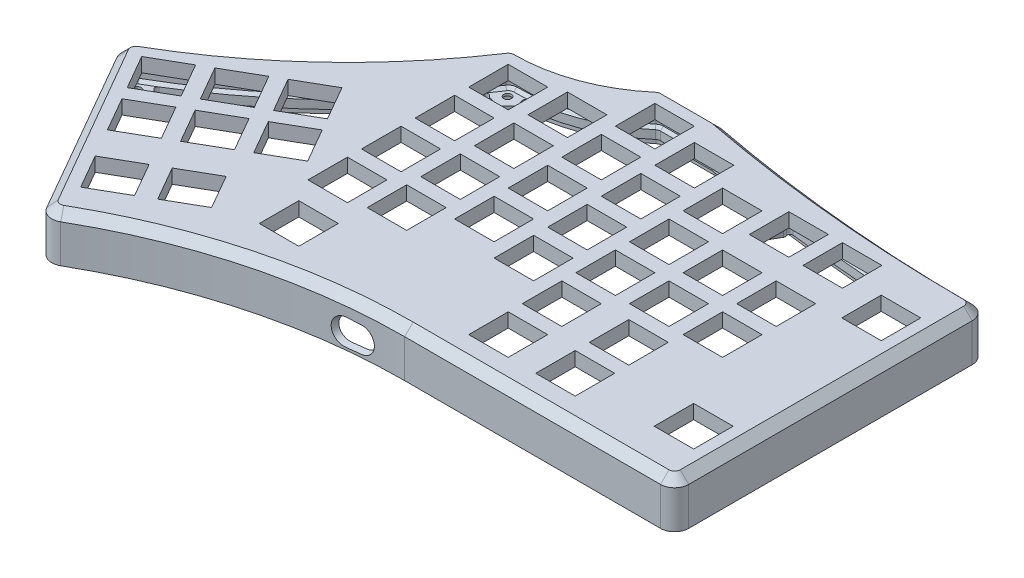
SolidWorks part; units mm, degrees
ref_plane "Front Plane" through (0, 0, 0) normal (0, 0, 1) x (1, 0, 0)
ref_plane "Top Plane" through (0, 0, 0) normal (0, 1, 0) x (1, 0, 0)
ref_plane "Right Plane" through (0, 0, 0) normal (1, 0, 0) x (0, 0, -1)
sketch "Main" plane through (0, 0, 0) normal (0, 1, 0) x (1, 0, 0)
  line L0 (6.4754, 3.5) -> (12.8, 6.5) construction
  line L1 (0, 0) -> (18, 0) construction
  line L2 (0, 0) -> (0, 18) construction
  line L3 (0, 18) -> (18, 18) construction
  line L4 (18, 0) -> (18, 18) construction
  line L5 (2, 16) -> (16, 16)
  line L6 (2, 16) -> (2, 2)
  line L7 (2, 2) -> (16, 2)
  line L8 (16, 16) -> (16, 2)
  line L18 (9, 9) -> (6.4754, 3.5) construction
  line L20 (9, 9) -> (12.8, 6.5) construction
  line L22 (25.4754, 5.5) -> (31.8, 8.5) construction
  line L23 (19, 2) -> (37, 2) construction
  line L24 (19, 2) -> (19, 20) construction
  line L25 (19, 20) -> (37, 20) construction
  line L26 (37, 2) -> (37, 20) construction
  line L27 (21, 18) -> (35, 18)
  line L28 (21, 18) -> (21, 4)
  line L29 (21, 4) -> (35, 4)
  line L30 (35, 18) -> (35, 4)
  line L31 (28, 11) -> (25.4754, 5.5) construction
  line L32 (28, 11) -> (31.8, 8.5) construction
  line L33 (44.4754, 17.5) -> (50.8, 20.5) construction
  line L34 (38, 14) -> (56, 14) construction
  line L35 (38, 14) -> (38, 32) construction
  line L36 (38, 32) -> (56, 32) construction
  line L37 (56, 14) -> (56, 32) construction
  line L38 (40, 30) -> (54, 30)
  line L39 (40, 30) -> (40, 16)
  line L40 (40, 16) -> (54, 16)
  line L41 (54, 30) -> (54, 16)
  line L42 (47, 23) -> (44.4754, 17.5) construction
  line L43 (47, 23) -> (50.8, 20.5) construction
  line L44 (63.4754, 12.5) -> (69.8, 15.5) construction
  line L45 (57, 9) -> (75, 9) construction
  line L46 (57, 9) -> (57, 27) construction
  line L47 (57, 27) -> (75, 27) construction
  line L48 (75, 9) -> (75, 27) construction
  line L49 (59, 25) -> (73, 25)
  line L50 (59, 25) -> (59, 11)
  line L51 (59, 11) -> (73, 11)
  line L52 (73, 25) -> (73, 11)
  line L53 (66, 18) -> (63.4754, 12.5) construction
  line L54 (66, 18) -> (69.8, 15.5) construction
  line L55 (82.4754, 3.5) -> (88.8, 6.5) construction
  line L56 (76, 0) -> (94, 0) construction
  line L57 (76, 0) -> (76, 18) construction
  line L58 (76, 18) -> (94, 18) construction
  line L59 (94, 0) -> (94, 18) construction
  line L60 (78, 16) -> (92, 16)
  line L61 (78, 16) -> (78, 2)
  line L62 (78, 2) -> (92, 2)
  line L63 (92, 16) -> (92, 2)
  line L64 (85, 9) -> (82.4754, 3.5) construction
  line L65 (85, 9) -> (88.8, 6.5) construction
  line L66 (101.4754, -15.5) -> (107.8, -12.5) construction
  line L67 (95, -19) -> (113, -19) construction
  line L68 (95, -19) -> (95, -1) construction
  line L69 (95, -1) -> (113, -1) construction
  line L70 (113, -19) -> (113, -1) construction
  line L71 (97, -3) -> (111, -3)
  line L72 (97, -3) -> (97, -17)
  line L73 (97, -17) -> (111, -17)
  line L74 (111, -3) -> (111, -17)
  line L75 (104, -10) -> (101.4754, -15.5) construction
  line L76 (104, -10) -> (107.8, -12.5) construction
  line L77 (120.4754, -15.5) -> (126.8, -12.5) construction
  line L78 (114, -19) -> (132, -19) construction
  line L79 (114, -19) -> (114, -1) construction
  line L80 (114, -1) -> (132, -1) construction
  line L81 (132, -19) -> (132, -1) construction
  line L82 (116, -3) -> (130, -3)
  line L83 (116, -3) -> (116, -17)
  line L84 (116, -17) -> (130, -17)
  line L85 (130, -3) -> (130, -17)
  line L86 (123, -10) -> (120.4754, -15.5) construction
  line L87 (123, -10) -> (126.8, -12.5) construction
  line L88 (2, -3) -> (16, -3)
  line L89 (2, -3) -> (2, -17)
  line L90 (2, -17) -> (16, -17)
  line L91 (16, -3) -> (16, -17)
  line L92 (21, -1) -> (35, -1)
  line L93 (21, -1) -> (21, -15)
  line L94 (21, -15) -> (35, -15)
  line L95 (35, -1) -> (35, -15)
  line L96 (40, 11) -> (54, 11)
  line L97 (40, 11) -> (40, -3)
  line L98 (40, -3) -> (54, -3)
  line L99 (54, 11) -> (54, -3)
  line L100 (59, 6) -> (73, 6)
  line L101 (59, 6) -> (59, -8)
  line L102 (59, -8) -> (73, -8)
  line L103 (73, 6) -> (73, -8)
  line L104 (78, -3) -> (92, -3)
  line L105 (78, -3) -> (78, -17)
  line L106 (78, -17) -> (92, -17)
  line L107 (92, -3) -> (92, -17)
  line L108 (97, -22) -> (111, -22)
  line L109 (97, -22) -> (97, -36)
  line L110 (97, -36) -> (111, -36)
  line L111 (111, -22) -> (111, -36)
  line L112 (116, -22) -> (130, -22)
  line L113 (116, -22) -> (116, -36)
  line L114 (116, -36) -> (130, -36)
  line L115 (130, -22) -> (130, -36)
  line L116 (6.4754, -15.5) -> (12.8, -12.5) construction
  line L117 (0, -19) -> (18, -19) construction
  line L118 (0, -19) -> (0, -1) construction
  line L119 (0, -1) -> (18, -1) construction
  line L120 (18, -19) -> (18, -1) construction
  line L121 (9, -10) -> (6.4754, -15.5) construction
  line L122 (9, -10) -> (12.8, -12.5) construction
  line L123 (25.4754, -13.5) -> (31.8, -10.5) construction
  line L124 (19, -17) -> (37, -17) construction
  line L125 (19, -17) -> (19, 1) construction
  line L126 (19, 1) -> (37, 1) construction
  line L127 (37, -17) -> (37, 1) construction
  line L128 (28, -8) -> (25.4754, -13.5) construction
  line L129 (28, -8) -> (31.8, -10.5) construction
  line L130 (44.4754, -1.5) -> (50.8, 1.5) construction
  line L131 (38, -5) -> (56, -5) construction
  line L132 (38, -5) -> (38, 13) construction
  line L133 (38, 13) -> (56, 13) construction
  line L134 (56, -5) -> (56, 13) construction
  line L135 (47, 4) -> (44.4754, -1.5) construction
  line L136 (47, 4) -> (50.8, 1.5) construction
  line L137 (63.4754, -6.5) -> (69.8, -3.5) construction
  line L138 (57, -10) -> (75, -10) construction
  line L139 (57, -10) -> (57, 8) construction
  line L140 (57, 8) -> (75, 8) construction
  line L141 (75, -10) -> (75, 8) construction
  line L142 (66, -1) -> (63.4754, -6.5) construction
  line L143 (66, -1) -> (69.8, -3.5) construction
  line L144 (82.4754, -15.5) -> (88.8, -12.5) construction
  line L145 (76, -19) -> (94, -19) construction
  line L146 (76, -19) -> (76, -1) construction
  line L147 (76, -1) -> (94, -1) construction
  line L148 (94, -19) -> (94, -1) construction
  line L149 (85, -10) -> (82.4754, -15.5) construction
  line L150 (85, -10) -> (88.8, -12.5) construction
  line L151 (101.4754, -34.5) -> (107.8, -31.5) construction
  line L152 (95, -38) -> (113, -38) construction
  line L153 (95, -38) -> (95, -20) construction
  line L154 (95, -20) -> (113, -20) construction
  line L155 (113, -38) -> (113, -20) construction
  line L156 (104, -29) -> (101.4754, -34.5) construction
  line L157 (104, -29) -> (107.8, -31.5) construction
  line L158 (120.4754, -34.5) -> (126.8, -31.5) construction
  line L159 (114, -38) -> (132, -38) construction
  line L160 (114, -38) -> (114, -20) construction
  line L161 (114, -20) -> (132, -20) construction
  line L162 (132, -38) -> (132, -20) construction
  line L163 (123, -29) -> (120.4754, -34.5) construction
  line L164 (123, -29) -> (126.8, -31.5) construction
  line L165 (2, -22) -> (16, -22)
  line L166 (2, -22) -> (2, -36)
  line L167 (2, -36) -> (16, -36)
  line L168 (16, -22) -> (16, -36)
  line L169 (21, -20) -> (35, -20)
  line L170 (21, -20) -> (21, -34)
  line L171 (21, -34) -> (35, -34)
  line L172 (35, -20) -> (35, -34)
  line L173 (40, -8) -> (54, -8)
  line L174 (40, -8) -> (40, -22)
  line L175 (40, -22) -> (54, -22)
  line L176 (54, -8) -> (54, -22)
  line L177 (59, -13) -> (73, -13)
  line L178 (59, -13) -> (59, -27)
  line L179 (59, -27) -> (73, -27)
  line L180 (73, -13) -> (73, -27)
  line L181 (78, -22) -> (92, -22)
  line L182 (78, -22) -> (78, -36)
  line L183 (78, -36) -> (92, -36)
  line L184 (92, -22) -> (92, -36)
  line L193 (6.4754, -34.5) -> (12.8, -31.5) construction
  line L194 (0, -38) -> (18, -38) construction
  line L195 (0, -38) -> (0, -20) construction
  line L196 (0, -20) -> (18, -20) construction
  line L197 (18, -38) -> (18, -20) construction
  line L198 (9, -29) -> (6.4754, -34.5) construction
  line L199 (9, -29) -> (12.8, -31.5) construction
  line L200 (25.4754, -32.5) -> (31.8, -29.5) construction
  line L201 (19, -36) -> (37, -36) construction
  line L202 (19, -36) -> (19, -18) construction
  line L203 (19, -18) -> (37, -18) construction
  line L204 (37, -36) -> (37, -18) construction
  line L205 (28, -27) -> (25.4754, -32.5) construction
  line L206 (28, -27) -> (31.8, -29.5) construction
  line L207 (44.4754, -20.5) -> (50.8, -17.5) construction
  line L208 (38, -24) -> (56, -24) construction
  line L209 (38, -24) -> (38, -6) construction
  line L210 (38, -6) -> (56, -6) construction
  line L211 (56, -24) -> (56, -6) construction
  line L212 (47, -15) -> (44.4754, -20.5) construction
  line L213 (47, -15) -> (50.8, -17.5) construction
  line L214 (63.4754, -25.5) -> (69.8, -22.5) construction
  line L215 (57, -29) -> (75, -29) construction
  line L216 (57, -29) -> (57, -11) construction
  line L217 (57, -11) -> (75, -11) construction
  line L218 (75, -29) -> (75, -11) construction
  line L219 (66, -20) -> (63.4754, -25.5) construction
  line L220 (66, -20) -> (69.8, -22.5) construction
  line L221 (82.4754, -34.5) -> (88.8, -31.5) construction
  line L222 (76, -38) -> (94, -38) construction
  line L223 (76, -38) -> (76, -20) construction
  line L224 (76, -20) -> (94, -20) construction
  line L225 (94, -38) -> (94, -20) construction
  line L226 (85, -29) -> (82.4754, -34.5) construction
  line L227 (85, -29) -> (88.8, -31.5) construction
  line L228 (97, 20.5) -> (111, 20.5)
  line L231 (97, 20.5) -> (97, 6.5)
  line L232 (97, 6.5) -> (111, 6.5)
  line L233 (111, 20.5) -> (111, 6.5)
  line L234 (116, 20.5) -> (130, 20.5)
  line L235 (116, 20.5) -> (116, 6.5)
  line L236 (116, 6.5) -> (130, 6.5)
  line L237 (130, 20.5) -> (130, 6.5)
  line L238 (101.4754, 8) -> (107.8, 11) construction
  line L239 (95, 4.5) -> (113, 4.5) construction
  line L240 (95, 4.5) -> (95, 22.5) construction
  line L241 (95, 22.5) -> (113, 22.5) construction
  line L242 (2, -41) -> (16, -41)
  line L243 (2, -41) -> (2, -55)
  line L244 (2, -55) -> (16, -55)
  line L245 (16, -41) -> (16, -55)
  line L246 (21, -39) -> (35, -39)
  line L247 (21, -39) -> (21, -53)
  line L248 (21, -53) -> (35, -53)
  line L249 (35, -39) -> (35, -53)
  line L250 (40, -27) -> (54, -27)
  line L251 (40, -27) -> (40, -41)
  line L252 (40, -41) -> (54, -41)
  line L253 (54, -27) -> (54, -41)
  line L254 (59, -32) -> (73, -32)
  line L255 (59, -32) -> (59, -46)
  line L256 (59, -46) -> (73, -46)
  line L257 (73, -32) -> (73, -46)
  line L258 (78, -41) -> (92, -41)
  line L259 (78, -41) -> (78, -55)
  line L260 (78, -55) -> (92, -55)
  line L261 (92, -41) -> (92, -55)
  line L270 (6.4754, -53.5) -> (12.8, -50.5) construction
  line L271 (0, -57) -> (18, -57) construction
  line L272 (0, -57) -> (0, -39) construction
  line L273 (0, -39) -> (18, -39) construction
  line L274 (18, -57) -> (18, -39) construction
  line L275 (9, -48) -> (6.4754, -53.5) construction
  line L276 (9, -48) -> (12.8, -50.5) construction
  line L277 (25.4754, -51.5) -> (31.8, -48.5) construction
  line L278 (19, -55) -> (37, -55) construction
  line L279 (19, -55) -> (19, -37) construction
  line L280 (19, -37) -> (37, -37) construction
  line L281 (37, -55) -> (37, -37) construction
  line L282 (28, -46) -> (25.4754, -51.5) construction
  line L283 (28, -46) -> (31.8, -48.5) construction
  line L284 (44.4754, -39.5) -> (50.8, -36.5) construction
  line L285 (38, -43) -> (56, -43) construction
  line L286 (38, -43) -> (38, -25) construction
  line L287 (38, -25) -> (56, -25) construction
  line L288 (56, -43) -> (56, -25) construction
  line L289 (47, -34) -> (44.4754, -39.5) construction
  line L290 (47, -34) -> (50.8, -36.5) construction
  line L291 (63.4754, -44.5) -> (69.8, -41.5) construction
  line L292 (57, -48) -> (75, -48) construction
  line L293 (57, -48) -> (57, -30) construction
  line L294 (57, -30) -> (75, -30) construction
  line L295 (75, -48) -> (75, -30) construction
  line L296 (66, -39) -> (63.4754, -44.5) construction
  line L297 (66, -39) -> (69.8, -41.5) construction
  line L298 (82.4754, -53.5) -> (88.8, -50.5) construction
  line L299 (76, -57) -> (94, -57) construction
  line L300 (76, -57) -> (76, -39) construction
  line L301 (76, -39) -> (94, -39) construction
  line L302 (94, -57) -> (94, -39) construction
  line L303 (85, -48) -> (82.4754, -53.5) construction
  line L304 (85, -48) -> (88.8, -50.5) construction
  line L305 (113, 4.5) -> (113, 22.5) construction
  line L306 (104, 13.5) -> (101.4754, 8) construction
  line L307 (104, 13.5) -> (107.8, 11) construction
  line L308 (120.4754, 8) -> (126.8, 11) construction
  line L309 (114, 4.5) -> (132, 4.5) construction
  line L310 (114, 4.5) -> (114, 22.5) construction
  line L311 (114, 22.5) -> (132, 22.5) construction
  line L312 (132, 4.5) -> (132, 22.5) construction
  line L313 (123, 13.5) -> (120.4754, 8) construction
  line L314 (123, 13.5) -> (126.8, 11) construction
  line L319 (97, -60) -> (111, -60)
  line L320 (97, -60) -> (97, -74)
  line L321 (97, -74) -> (111, -74)
  line L322 (111, -60) -> (111, -74)
  line L323 (116, -60) -> (130, -60)
  line L324 (116, -60) -> (116, -74)
  line L325 (116, -74) -> (130, -74)
  line L326 (130, -60) -> (130, -74)
  line L327 (101.4754, -72.5) -> (107.8, -69.5) construction
  line L328 (95, -76) -> (113, -76) construction
  line L329 (95, -76) -> (95, -58) construction
  line L330 (95, -58) -> (113, -58) construction
  line L331 (113, -76) -> (113, -58) construction
  line L332 (104, -67) -> (101.4754, -72.5) construction
  line L333 (104, -67) -> (107.8, -69.5) construction
  line L334 (120.4754, -72.5) -> (126.8, -69.5) construction
  line L335 (114, -76) -> (132, -76) construction
  line L336 (114, -76) -> (114, -58) construction
  line L337 (114, -58) -> (132, -58) construction
  line L338 (132, -76) -> (132, -58) construction
  line L339 (123, -67) -> (120.4754, -72.5) construction
  line L340 (123, -67) -> (126.8, -69.5) construction
  line L341 (97, -41) -> (111, -41)
  line L342 (97, -41) -> (97, -55)
  line L343 (97, -55) -> (111, -55)
  line L344 (111, -41) -> (111, -55)
  line L345 (116, -41) -> (130, -41)
  line L346 (116, -41) -> (116, -55)
  line L347 (116, -55) -> (130, -55)
  line L348 (130, -41) -> (130, -55)
  line L349 (101.4754, -53.5) -> (107.8, -50.5) construction
  line L350 (95, -39) -> (113, -39) construction
  line L351 (113, -57) -> (113, -39) construction
  line L352 (104, -48) -> (101.4754, -53.5) construction
  line L353 (104, -48) -> (107.8, -50.5) construction
  line L354 (120.4754, -53.5) -> (126.8, -50.5) construction
  line L355 (114, -57) -> (132, -57) construction
  line L356 (114, -57) -> (114, -39) construction
  line L357 (114, -39) -> (132, -39) construction
  line L358 (132, -57) -> (132, -39) construction
  line L359 (123, -48) -> (120.4754, -53.5) construction
  line L360 (123, -48) -> (126.8, -50.5) construction
  line L361 (95, -57) -> (113, -57) construction
  line L362 (95, -57) -> (95, -39) construction
  circle A0 centre (9, 9) radius 2 construction
  circle A1 centre (6.4754, 3.5) radius 1.5 construction
  circle A2 centre (12.8, 6.5) radius 1.5 construction
  circle A6 centre (28, 11) radius 2 construction
  circle A7 centre (25.4754, 5.5) radius 1.5 construction
  circle A8 centre (31.8, 8.5) radius 1.5 construction
  circle A9 centre (47, 23) radius 2 construction
  circle A10 centre (44.4754, 17.5) radius 1.5 construction
  circle A11 centre (50.8, 20.5) radius 1.5 construction
  circle A12 centre (66, 18) radius 2 construction
  circle A13 centre (63.4754, 12.5) radius 1.5 construction
  circle A14 centre (69.8, 15.5) radius 1.5 construction
  circle A15 centre (85, 9) radius 2 construction
  circle A16 centre (82.4754, 3.5) radius 1.5 construction
  circle A17 centre (88.8, 6.5) radius 1.5 construction
  circle A18 centre (104, -10) radius 2 construction
  circle A19 centre (101.4754, -15.5) radius 1.5 construction
  circle A20 centre (107.8, -12.5) radius 1.5 construction
  circle A21 centre (123, -10) radius 2 construction
  circle A22 centre (120.4754, -15.5) radius 1.5 construction
  circle A23 centre (126.8, -12.5) radius 1.5 construction
  circle A24 centre (9, -10) radius 2 construction
  circle A25 centre (6.4754, -15.5) radius 1.5 construction
  circle A26 centre (12.8, -12.5) radius 1.5 construction
  circle A27 centre (28, -8) radius 2 construction
  circle A28 centre (25.4754, -13.5) radius 1.5 construction
  circle A29 centre (31.8, -10.5) radius 1.5 construction
  circle A30 centre (47, 4) radius 2 construction
  circle A31 centre (44.4754, -1.5) radius 1.5 construction
  circle A32 centre (50.8, 1.5) radius 1.5 construction
  circle A33 centre (66, -1) radius 2 construction
  circle A34 centre (63.4754, -6.5) radius 1.5 construction
  circle A35 centre (69.8, -3.5) radius 1.5 construction
  circle A36 centre (85, -10) radius 2 construction
  circle A37 centre (82.4754, -15.5) radius 1.5 construction
  circle A38 centre (88.8, -12.5) radius 1.5 construction
  circle A39 centre (104, -29) radius 2 construction
  circle A40 centre (101.4754, -34.5) radius 1.5 construction
  circle A41 centre (107.8, -31.5) radius 1.5 construction
  circle A42 centre (123, -29) radius 2 construction
  circle A43 centre (120.4754, -34.5) radius 1.5 construction
  circle A44 centre (126.8, -31.5) radius 1.5 construction
  circle A45 centre (9, -29) radius 2 construction
  circle A46 centre (6.4754, -34.5) radius 1.5 construction
  circle A47 centre (12.8, -31.5) radius 1.5 construction
  circle A48 centre (28, -27) radius 2 construction
  circle A49 centre (25.4754, -32.5) radius 1.5 construction
  circle A50 centre (31.8, -29.5) radius 1.5 construction
  circle A51 centre (47, -15) radius 2 construction
  circle A52 centre (44.4754, -20.5) radius 1.5 construction
  circle A53 centre (50.8, -17.5) radius 1.5 construction
  circle A54 centre (66, -20) radius 2 construction
  circle A55 centre (63.4754, -25.5) radius 1.5 construction
  circle A56 centre (69.8, -22.5) radius 1.5 construction
  circle A57 centre (85, -29) radius 2 construction
  circle A58 centre (82.4754, -34.5) radius 1.5 construction
  circle A59 centre (88.8, -31.5) radius 1.5 construction
  circle A60 centre (104, 13.5) radius 2 construction
  circle A61 centre (101.4754, 8) radius 1.5 construction
  circle A62 centre (107.8, 11) radius 1.5 construction
  circle A63 centre (123, 13.5) radius 2 construction
  circle A64 centre (120.4754, 8) radius 1.5 construction
  circle A65 centre (126.8, 11) radius 1.5 construction
  circle A66 centre (9, -48) radius 2 construction
  circle A67 centre (6.4754, -53.5) radius 1.5 construction
  circle A68 centre (12.8, -50.5) radius 1.5 construction
  circle A69 centre (28, -46) radius 2 construction
  circle A70 centre (25.4754, -51.5) radius 1.5 construction
  circle A71 centre (31.8, -48.5) radius 1.5 construction
  circle A72 centre (47, -34) radius 2 construction
  circle A73 centre (44.4754, -39.5) radius 1.5 construction
  circle A74 centre (50.8, -36.5) radius 1.5 construction
  circle A75 centre (66, -39) radius 2 construction
  circle A76 centre (63.4754, -44.5) radius 1.5 construction
  circle A77 centre (69.8, -41.5) radius 1.5 construction
  circle A78 centre (85, -48) radius 2 construction
  circle A79 centre (82.4754, -53.5) radius 1.5 construction
  circle A80 centre (88.8, -50.5) radius 1.5 construction
  circle A87 centre (104, -67) radius 2 construction
  circle A88 centre (101.4754, -72.5) radius 1.5 construction
  circle A89 centre (107.8, -69.5) radius 1.5 construction
  circle A90 centre (123, -67) radius 2 construction
  circle A91 centre (120.4754, -72.5) radius 1.5 construction
  circle A92 centre (126.8, -69.5) radius 1.5 construction
  circle A93 centre (104, -48) radius 2 construction
  circle A94 centre (101.4754, -53.5) radius 1.5 construction
  circle A95 centre (107.8, -50.5) radius 1.5 construction
  circle A96 centre (123, -48) radius 2 construction
  circle A97 centre (120.4754, -53.5) radius 1.5 construction
  circle A98 centre (126.8, -50.5) radius 1.5 construction
  point P9 (9, 16)
  point P10 (9, 18)
  point P11 (2, 9)
  point P12 (0, 9)
  point P30 (28, 18)
  point P31 (28, 20)
  point P32 (21, 11)
  point P33 (19, 11)
  point P46 (47, 30)
  point P47 (47, 32)
  point P48 (40, 23)
  point P49 (38, 23)
  point P64 (66, 25)
  point P65 (66, 27)
  point P66 (59, 18)
  point P67 (57, 18)
  point P82 (85, 16)
  point P83 (85, 18)
  point P84 (78, 9)
  point P85 (76, 9)
  point P100 (104, -3)
  point P101 (104, -1)
  point P102 (97, -10)
  point P103 (95, -10)
  point P118 (123, -3)
  point P119 (123, -1)
  point P120 (116, -10)
  point P121 (114, -10)
  dimension "D6" = 4
  dimension "D7" = 3
  dimension "D10" = 1
  dimension "D11" = 5
  dimension "D1" = 18
  dimension "D2" = 14
  dimension "D3" = 3.2
  dimension "D4" = 4.5
  dimension "D5" = 7
  dimension "D8" = 1
  dimension "D9" = 12
  dimension "D12" = 1
  dimension "D13" = 2
  dimension "D14" = 1
  dimension "D15" = 9
  dimension "D16" = 1
  dimension "D18" = 1
  dimension "D20" = 1
  dimension "D22" = 4.5
  dimension "D19" = 4
  dimension "D21" = 2
sketch "EntBckSp" plane through (0, 0, 0) normal (0, 1, 0) x (1, 0, 0)
  line L0 (0, 0) -> (18, 0) construction
  line L1 (139, 11.25) -> (153, 11.25)
  line L2 (139, 11.25) -> (139, -2.75)
  line L3 (139, -2.75) -> (153, -2.75)
  line L4 (153, 11.25) -> (153, -2.75)
  line L5 (137, 18) -> (155, 18) construction
  line L6 (137, 18) -> (137, -9.5) construction
  line L7 (137, -9.5) -> (155, -9.5) construction
  line L8 (155, 18) -> (155, -9.5) construction
  line L9 (2, 2) -> (16, 2) construction
  line L10 (143.4754, -1.25) -> (146, 4.25) construction
  line L11 (146, 4.25) -> (149.8, 1.75) construction
  line L12 (149.8, 1.75) -> (143.4754, -1.25) construction
  line L13 (6.4754, 3.5) -> (12.8, 6.5) construction
  line L14 (9, 9) -> (6.4754, 3.5) construction
  line L15 (9, 9) -> (12.8, 6.5) construction
  line L16 (2, -55) -> (16, -55) construction
  line L17 (132, -19) -> (132, -1) construction
  line L18 (101.75, -41) -> (115.75, -41)
  line L19 (101.75, -41) -> (101.75, -55)
  line L20 (101.75, -55) -> (115.75, -55)
  line L21 (115.75, -41) -> (115.75, -55)
  line L22 (95, -39) -> (122.5, -39) construction
  line L23 (95, -39) -> (95, -57) construction
  line L24 (95, -57) -> (122.5, -57) construction
  line L25 (122.5, -39) -> (122.5, -57) construction
  line L26 (106.2254, -53.5) -> (108.75, -48) construction
  line L27 (108.75, -48) -> (112.55, -50.5) construction
  line L28 (112.55, -50.5) -> (106.2254, -53.5) construction
  line L29 (0, 18) -> (18, 18) construction
  line L30 (46.5, -79) -> (28.5, -79) construction
  line L31 (101.75, -60) -> (115.75, -60)
  line L32 (101.75, -60) -> (101.75, -74)
  line L33 (101.75, -74) -> (115.75, -74)
  line L34 (115.75, -60) -> (115.75, -74)
  line L35 (95, -58) -> (122.5, -58) construction
  line L36 (95, -58) -> (95, -76) construction
  line L37 (95, -76) -> (122.5, -76) construction
  line L38 (122.5, -58) -> (122.5, -76) construction
  line L39 (106.2254, -72.5) -> (108.75, -67) construction
  line L40 (108.75, -67) -> (112.55, -69.5) construction
  line L41 (112.55, -69.5) -> (106.2254, -72.5) construction
  line L42 (139, -55.25) -> (153, -55.25)
  line L43 (139, -55.25) -> (139, -69.25)
  line L44 (139, -69.25) -> (153, -69.25)
  line L45 (153, -55.25) -> (153, -69.25)
  line L46 (137, -48.5) -> (155, -48.5) construction
  line L47 (137, -48.5) -> (137, -76) construction
  line L48 (137, -76) -> (155, -76) construction
  line L49 (155, -48.5) -> (155, -76) construction
  line L50 (143.4754, -67.75) -> (146, -62.25) construction
  line L51 (146, -62.25) -> (149.8, -64.75) construction
  line L52 (149.8, -64.75) -> (143.4754, -67.75) construction
  line L64 (95, -38) -> (95, -20) construction
  line L65 (114, -38) -> (132, -38) construction
  line L66 (6.75, -63) -> (20.75, -63)
  line L67 (6.75, -63) -> (6.75, -77)
  line L68 (6.75, -77) -> (20.75, -77)
  line L69 (20.75, -63) -> (20.75, -77)
  line L70 (0, -61) -> (27.5, -61) construction
  line L71 (0, -61) -> (0, -79) construction
  line L72 (0, -79) -> (27.5, -79) construction
  line L73 (27.5, -61) -> (27.5, -79) construction
  line L74 (11.2254, -75.5) -> (13.75, -70) construction
  line L75 (13.75, -70) -> (17.55, -72.5) construction
  line L76 (17.55, -72.5) -> (11.2254, -75.5) construction
  line L77 (88.8, -69.5) -> (85, -67) construction
  line L78 (0, -57) -> (0, -39) construction
  line L79 (78, -74) -> (92, -74)
  line L80 (30.5, -63) -> (44.5, -63) construction
  line L81 (30.5, -63) -> (30.5, -77) construction
  line L82 (30.5, -77) -> (44.5, -77) construction
  line L83 (44.5, -63) -> (44.5, -77) construction
  line L86 (34.9754, -75.5) -> (37.5, -70) construction
  line L87 (37.5, -70) -> (41.3, -72.5) construction
  line L88 (41.3, -72.5) -> (34.9754, -75.5) construction
  line L91 (51.25, -61) -> (51.25, -79) construction
  line L92 (23.75, -61) -> (23.75, -79) construction
  line L93 (46.5, -79) -> (46.5, -61) construction
  line L94 (46.5, -61) -> (28.5, -61) construction
  line L95 (28.5, -79) -> (28.5, -61) construction
  line L96 (78, -74) -> (78, -60)
  line L97 (78, -60) -> (92, -60)
  line L98 (92, -74) -> (92, -60)
  line L99 (78, -74) -> (92, -60) construction
  line L100 (92, -41) -> (92, -55) construction
  line L101 (85, -67) -> (82.4754, -72.5) construction
  line L102 (82.4754, -72.5) -> (88.8, -69.5) construction
  line L104 (76, -58) -> (94, -58) construction
  line L105 (76, -58) -> (76, -76) construction
  line L106 (76, -76) -> (94, -76) construction
  line L107 (94, -58) -> (94, -76) construction
  line L108 (76, -58) -> (94, -76) construction
  circle A0 centre (146, 4.25) radius 2 construction
  circle A1 centre (143.4754, -1.25) radius 1.5 construction
  circle A2 centre (149.8, 1.75) radius 1.5 construction
  circle A3 centre (9, 9) radius 2 construction
  circle A4 centre (6.4754, 3.5) radius 1.5 construction
  circle A5 centre (108.75, -48) radius 2 construction
  circle A6 centre (106.2254, -53.5) radius 1.5 construction
  circle A7 centre (112.55, -50.5) radius 1.5 construction
  circle A8 centre (108.75, -67) radius 2 construction
  circle A9 centre (106.2254, -72.5) radius 1.5 construction
  circle A10 centre (112.55, -69.5) radius 1.5 construction
  circle A11 centre (146, -62.25) radius 2 construction
  circle A12 centre (143.4754, -67.75) radius 1.5 construction
  circle A13 centre (149.8, -64.75) radius 1.5 construction
  circle A17 centre (13.75, -70) radius 2 construction
  circle A18 centre (11.2254, -75.5) radius 1.5 construction
  circle A19 centre (17.55, -72.5) radius 1.5 construction
  circle A20 centre (37.5, -70) radius 2 construction
  circle A21 centre (34.9754, -75.5) radius 1.5 construction
  circle A22 centre (41.3, -72.5) radius 1.5 construction
  circle A23 centre (85, -67) radius 2 construction
  circle A24 centre (88.8, -69.5) radius 1.5 construction
  circle A25 centre (82.4754, -72.5) radius 1.5 construction
  point P14 (146, 11.25)
  point P15 (146, 18)
  point P16 (139, 4.25)
  point P17 (137, 4.25)
  point P51 (108.75, -41)
  point P52 (108.75, -39)
  point P53 (101.75, -48)
  point P54 (95, -48)
  point P87 (146, -55.25)
  point P88 (146, -48.5)
  point P89 (139, -62.25)
  point P90 (137, -62.25)
  point P105 (13.75, -63)
  point P106 (13.75, -61)
  point P107 (6.75, -70)
  point P108 (0, -70)
  point P109 (37.5, -63)
  point P132 (37.5, -61)
  dimension "D1" = 27.5
  dimension "D2" = 5
  dimension "D3" = 1
  dimension "D5" = 1
  dimension "D6" = 2
  dimension "D7" = 1
  dimension "D8" = 8
  dimension "D4" = 2
sketch "MoLng" plane through (0, 0, 0) normal (0, 1, 0) x (1, 0, 0)
  line L0 (-25.7133, -75.4047) -> (-13.5763, -68.4267)
  line L1 (-25.7133, -75.4047) -> (-18.7353, -87.5417)
  line L2 (-13.5763, -68.4267) -> (-6.5983, -80.5637)
  line L3 (-18.7353, -87.5417) -> (-6.5983, -80.5637)
  line L4 (-30.8116, -70.5498) -> (-15.2068, -61.578) construction
  line L5 (-30.8116, -70.5498) -> (-17.1047, -94.3903) construction
  line L6 (-15.2068, -61.578) -> (-1.5, -85.4186) construction
  line L7 (-17.1047, -94.3903) -> (-1.5, -85.4186) construction
  line L8 (-15.2068, -61.578) -> (-17.1047, -94.3903) construction
  line L9 (-25.7133, -75.4047) -> (-6.5983, -80.5637) construction
  line L10 (0, -61) -> (0, -79) construction
  line L11 (0, -79) -> (27.5, -79) construction
  line L12 (6.75, -77) -> (20.75, -77) construction
  line L13 (-16.1558, -77.9842) -> (13.75, -130) construction
  line L14 (-15.603, -84.0106) -> (-11.6154, -78.2575) construction
  line L15 (-11.6154, -78.2575) -> (-16.1558, -77.9842) construction
  line L16 (-16.1558, -77.9842) -> (-15.603, -84.0106) construction
  line L17 (17.55, -72.5) -> (11.2254, -75.5) construction
  line L18 (11.2254, -75.5) -> (13.75, -70) construction
  line L19 (13.75, -70) -> (17.55, -72.5) construction
  line L20 (-43.0519, -85.3733) -> (-30.9149, -78.3953)
  line L21 (-43.0519, -85.3733) -> (-36.0739, -97.5103)
  line L22 (-30.9149, -78.3953) -> (-23.9369, -90.5323)
  line L23 (-36.0739, -97.5103) -> (-23.9369, -90.5323)
  line L24 (-48.1502, -80.5184) -> (-32.5454, -71.5466) construction
  line L25 (-48.1502, -80.5184) -> (-34.4433, -104.3589) construction
  line L26 (-32.5454, -71.5466) -> (-18.8386, -95.3872) construction
  line L27 (-34.4433, -104.3589) -> (-18.8386, -95.3872) construction
  line L28 (-32.5454, -71.5466) -> (-34.4433, -104.3589) construction
  line L29 (-43.0519, -85.3733) -> (-23.9369, -90.5323) construction
  line L31 (-32.9416, -93.9792) -> (-28.954, -88.2261) construction
  line L32 (-28.954, -88.2261) -> (-33.4944, -87.9528) construction
  line L33 (-33.4944, -87.9528) -> (-32.9416, -93.9792) construction
  line L38 (-48.9084, -75.1869) -> (-55.8865, -63.0498)
  line L39 (-48.9084, -75.1869) -> (-36.7714, -68.2088)
  line L43 (-55.8865, -63.0498) -> (-43.7494, -56.0718)
  line L51 (-36.7714, -68.2088) -> (-43.7494, -56.0718)
  line L52 (-48.9084, -75.1869) -> (-43.7494, -56.0718) construction
  line L56 (-55.8865, -63.0498) -> (-36.7714, -68.2088) construction
  line L57 (2, -55) -> (16, -55) construction
  line L58 (-45.7762, -71.6558) -> (-41.7885, -65.9026) construction
  line L59 (-41.7885, -65.9026) -> (-46.3289, -65.6293) construction
  line L66 (-46.3289, -65.6293) -> (-45.7762, -71.6558) construction
  line L69 (9, -48) -> (12.8, -50.5) construction
  line L70 (6.4754, -53.5) -> (12.8, -50.5) construction
  line L71 (9, -48) -> (6.4754, -53.5) construction
  line L73 (-49.6455, -77.9176) -> (-58.6172, -62.3128) construction
  line L104 (-49.6455, -77.9176) -> (-34.0407, -68.9458) construction
  line L134 (-58.6172, -62.3128) -> (-43.0124, -53.3411) construction
  line L135 (-34.0407, -68.9458) -> (-43.0124, -53.3411) construction
  line L136 (-49.6455, -77.9176) -> (-43.0124, -53.3411) construction
  line L137 (-58.6172, -62.3128) -> (-34.0407, -68.9458) construction
  line L158 (0, -57) -> (18, -57) construction
  line L162 (-32.4368, -65.7167) -> (-39.4148, -53.5797)
  line L163 (-32.4368, -65.7167) -> (-20.2998, -58.7387)
  line L170 (-39.4148, -53.5797) -> (-27.2778, -46.6017)
  line L171 (-20.2998, -58.7387) -> (-27.2778, -46.6017)
  line L174 (-32.4368, -65.7167) -> (-27.2778, -46.6017) construction
  line L175 (-39.4148, -53.5797) -> (-20.2998, -58.7387) construction
  line L176 (-29.3045, -62.1856) -> (-25.3169, -56.4325) construction
  line L177 (-25.3169, -56.4325) -> (-29.8573, -56.1592) construction
  line L180 (-29.8573, -56.1592) -> (-29.3045, -62.1856) construction
  line L181 (-33.1738, -68.4474) -> (-42.1455, -52.8427) construction
  line L182 (-33.1738, -68.4474) -> (-17.569, -59.4757) construction
  line L183 (-42.1455, -52.8427) -> (-26.5408, -43.8709) construction
  line L184 (-17.569, -59.4757) -> (-26.5408, -43.8709) construction
  line L185 (-33.1738, -68.4474) -> (-26.5408, -43.8709) construction
  line L190 (-42.1455, -52.8427) -> (-17.569, -59.4757) construction
  line L191 (-15.9651, -56.2465) -> (-22.9431, -44.1095)
  line L192 (-15.9651, -56.2465) -> (-3.8281, -49.2685)
  line L193 (-22.9431, -44.1095) -> (-10.8061, -37.1315)
  line L194 (-3.8281, -49.2685) -> (-10.8061, -37.1315)
  line L195 (-15.9651, -56.2465) -> (-10.8061, -37.1315) construction
  line L196 (-22.9431, -44.1095) -> (-3.8281, -49.2685) construction
  line L197 (-12.8328, -52.7154) -> (-8.8452, -46.9623) construction
  line L198 (-8.8452, -46.9623) -> (-13.3856, -46.689) construction
  line L199 (-13.3856, -46.689) -> (-12.8328, -52.7154) construction
  line L200 (-16.7021, -58.9772) -> (-25.6738, -43.3725) construction
  line L201 (-16.7021, -58.9772) -> (-1.0974, -50.0055) construction
  line L202 (-25.6738, -43.3725) -> (-10.0691, -34.4008) construction
  line L203 (-1.0974, -50.0055) -> (-10.0691, -34.4008) construction
  line L204 (-16.7021, -58.9772) -> (-10.0691, -34.4008) construction
  line L205 (-25.6738, -43.3725) -> (-1.0974, -50.0055) construction
  line L206 (-41.9069, -49.245) -> (-48.885, -37.108)
  line L207 (-41.9069, -49.245) -> (-29.7699, -42.267)
  line L208 (-48.885, -37.108) -> (-36.7479, -30.13)
  line L209 (-29.7699, -42.267) -> (-36.7479, -30.13)
  line L210 (-41.9069, -49.245) -> (-36.7479, -30.13) construction
  line L211 (-48.885, -37.108) -> (-29.7699, -42.267) construction
  line L212 (-38.7747, -45.7139) -> (-34.787, -39.9608) construction
  line L213 (-34.787, -39.9608) -> (-39.3274, -39.6875) construction
  line L214 (-39.3274, -39.6875) -> (-38.7747, -45.7139) construction
  line L215 (-42.6439, -51.9757) -> (-51.6157, -36.371) construction
  line L216 (-42.6439, -51.9757) -> (-27.0392, -43.004) construction
  line L217 (-51.6157, -36.371) -> (-36.0109, -27.3993) construction
  line L218 (-27.0392, -43.004) -> (-36.0109, -27.3993) construction
  line L219 (-42.6439, -51.9757) -> (-36.0109, -27.3993) construction
  line L220 (-51.6157, -36.371) -> (-27.0392, -43.004) construction
  line L221 (-25.4353, -39.7749) -> (-32.4133, -27.6378)
  line L222 (-25.4353, -39.7749) -> (-13.2982, -32.7968)
  line L223 (-32.4133, -27.6378) -> (-20.2763, -20.6598)
  line L224 (-13.2982, -32.7968) -> (-20.2763, -20.6598)
  line L225 (-25.4353, -39.7749) -> (-20.2763, -20.6598) construction
  line L226 (-32.4133, -27.6378) -> (-13.2982, -32.7968) construction
  line L227 (-22.303, -36.2438) -> (-18.3154, -30.4906) construction
  line L228 (-18.3154, -30.4906) -> (-22.8558, -30.2173) construction
  line L229 (-22.8558, -30.2173) -> (-22.303, -36.2438) construction
  line L230 (-26.1723, -42.5056) -> (-35.144, -26.9008) construction
  line L231 (-26.1723, -42.5056) -> (-10.5675, -33.5338) construction
  line L232 (-35.144, -26.9008) -> (-19.5393, -17.9291) construction
  line L233 (-10.5675, -33.5338) -> (-19.5393, -17.9291) construction
  line L234 (-26.1723, -42.5056) -> (-19.5393, -17.9291) construction
  line L235 (-35.144, -26.9008) -> (-10.5675, -33.5338) construction
  line L236 (-58.3786, -58.7152) -> (-65.3566, -46.5782)
  line L237 (-58.3786, -58.7152) -> (-46.2416, -51.7372)
  line L238 (-65.3566, -46.5782) -> (-53.2196, -39.6001)
  line L239 (-46.2416, -51.7372) -> (-53.2196, -39.6001)
  line L240 (-58.3786, -58.7152) -> (-53.2196, -39.6001) construction
  line L241 (-65.3566, -46.5782) -> (-46.2416, -51.7372) construction
  line L242 (-55.2464, -55.1841) -> (-51.2587, -49.431) construction
  line L243 (-51.2587, -49.431) -> (-55.7991, -49.1577) construction
  line L244 (-55.7991, -49.1577) -> (-55.2464, -55.1841) construction
  line L245 (-59.1156, -61.4459) -> (-68.0873, -45.8412) construction
  line L246 (-59.1156, -61.4459) -> (-43.5109, -52.4742) construction
  line L247 (-68.0873, -45.8412) -> (-52.4826, -36.8694) construction
  line L248 (-43.5109, -52.4742) -> (-52.4826, -36.8694) construction
  line L249 (-59.1156, -61.4459) -> (-52.4826, -36.8694) construction
  line L250 (-68.0873, -45.8412) -> (-43.5109, -52.4742) construction
  circle A0 centre (13.75, -130) radius 60 construction
  circle A1 centre (-16.1558, -77.9842) radius 2 construction
  circle A2 centre (13.75, -70) radius 2 construction
  circle A3 centre (-15.603, -84.0106) radius 1.5 construction
  circle A4 centre (-11.6154, -78.2575) radius 1.5 construction
  circle A5 centre (11.2254, -75.5) radius 1.5 construction
  circle A6 centre (-33.4944, -87.9528) radius 2 construction
  circle A7 centre (-32.9416, -93.9792) radius 1.5 construction
  circle A8 centre (-28.954, -88.2261) radius 1.5 construction
  circle A12 centre (-46.3289, -65.6293) radius 2 construction
  circle A13 centre (-45.7762, -71.6558) radius 1.5 construction
  circle A14 centre (-41.7885, -65.9026) radius 1.5 construction
  circle A15 centre (6.4754, -53.5) radius 1.5 construction
  circle A16 centre (9, -48) radius 2 construction
  circle A17 centre (-29.8573, -56.1592) radius 2 construction
  circle A18 centre (-25.3169, -56.4325) radius 1.5 construction
  circle A19 centre (-29.3045, -62.1856) radius 1.5 construction
  circle A20 centre (-13.3856, -46.689) radius 2 construction
  circle A24 centre (-8.8452, -46.9623) radius 1.5 construction
  circle A25 centre (-12.8328, -52.7154) radius 1.5 construction
  circle A26 centre (-39.3274, -39.6875) radius 2 construction
  circle A27 centre (-34.787, -39.9608) radius 1.5 construction
  circle A28 centre (-38.7747, -45.7139) radius 1.5 construction
  circle A29 centre (-22.8558, -30.2173) radius 2 construction
  circle A30 centre (-18.3154, -30.4906) radius 1.5 construction
  circle A31 centre (-22.303, -36.2438) radius 1.5 construction
  circle A32 centre (-55.7991, -49.1577) radius 2 construction
  circle A35 centre (-51.2587, -49.431) radius 1.5 construction
  circle A36 centre (-55.2464, -55.1841) radius 1.5 construction
  point P2 (-16.1558, -77.9842)
  point P11 (-16.1558, -77.9842)
  point P28 (-46.3289, -65.6293)
  point P39 (-33.4944, -87.9528)
  point P46 (-33.4944, -87.9528)
  point P89 (-29.8573, -56.1592)
  point P112 (-13.3856, -46.689)
  point P134 (-39.3274, -39.6875)
  point P155 (-22.8558, -30.2173)
  point P170 (-55.7991, -49.1577)
  dimension "D1" = 120
  dimension "D2" = 2
  dimension "D4" = 2
  dimension "D5" = 3
  dimension "D6" = 1.5
  dimension "D8" = 1
  dimension "D3" = 3
  dimension "D7" = 1
sketch "Sketch3" plane through (0, 0, 0) normal (0, 1, 0) x (1, 0, 0)
  line L1 (160, 22.5) -> (160, -78)
  line L2 (155, -83) -> (64.2873, -83)
  line L8 (-34.4433, -104.3589) -> (-31.9512, -108.6936) construction
  line L9 (155, -48.5) -> (155, -76) construction
  line L10 (-48.1502, -80.5184) -> (-34.4433, -104.3589) construction
  line L11 (-34.4433, -104.3589) -> (-18.8386, -95.3872) construction
  line L12 (-38.778, -106.8511) -> (-72.422, -48.3333)
  line L13 (0, 23) -> (40, 23) construction
  line L14 (38, 14) -> (38, 32) construction
  line L15 (38, 35) -> (56, 35) construction
  line L16 (38, 32) -> (56, 32) construction
  line L18 (97, 20.5) -> (111, 20.5)
  line L19 (-65.3566, -46.5782) -> (-53.2196, -39.6001)
  line L22 (2, -3) -> (16, -3)
  line L23 (2, 16) -> (16, 16)
  line L24 (2, 16) -> (2, 2)
  line L25 (2, 2) -> (16, 2)
  line L26 (16, 16) -> (16, 2)
  line L27 (21, 18) -> (35, 18)
  line L28 (21, 18) -> (21, 4)
  line L29 (21, 4) -> (35, 4)
  line L30 (35, 18) -> (35, 4)
  line L31 (40, 30) -> (54, 30)
  line L32 (40, 30) -> (40, 16)
  line L33 (40, 16) -> (54, 16)
  line L34 (54, 30) -> (54, 16)
  line L35 (59, 25) -> (73, 25)
  line L36 (59, 25) -> (59, 11)
  line L37 (59, 11) -> (73, 11)
  line L38 (73, 25) -> (73, 11)
  line L39 (78, 16) -> (92, 16)
  line L40 (78, 16) -> (78, 2)
  line L41 (78, 2) -> (92, 2)
  line L42 (92, 16) -> (92, 2)
  line L43 (97, -3) -> (111, -3)
  line L44 (97, -3) -> (97, -17)
  line L45 (97, -17) -> (111, -17)
  line L46 (111, -3) -> (111, -17)
  line L47 (116, -3) -> (130, -3)
  line L48 (116, -3) -> (116, -17)
  line L49 (116, -17) -> (130, -17)
  line L50 (130, -3) -> (130, -17)
  line L51 (139, 11.25) -> (153, 11.25)
  line L52 (139, 11.25) -> (139, -2.75)
  line L53 (139, -2.75) -> (153, -2.75)
  line L54 (153, 11.25) -> (153, -2.75)
  line L55 (139, -55.25) -> (153, -55.25)
  line L56 (139, -55.25) -> (139, -69.25)
  line L57 (139, -69.25) -> (153, -69.25)
  line L58 (153, -55.25) -> (153, -69.25)
  line L59 (2, -3) -> (2, -17)
  line L60 (2, -17) -> (16, -17)
  line L61 (16, -3) -> (16, -17)
  line L62 (21, -1) -> (35, -1)
  line L63 (21, -1) -> (21, -15)
  line L64 (21, -15) -> (35, -15)
  line L65 (35, -1) -> (35, -15)
  line L66 (40, 11) -> (54, 11)
  line L67 (40, 11) -> (40, -3)
  line L68 (40, -3) -> (54, -3)
  line L69 (54, 11) -> (54, -3)
  line L70 (59, 6) -> (73, 6)
  line L71 (59, 6) -> (59, -8)
  line L72 (59, -8) -> (73, -8)
  line L73 (73, 6) -> (73, -8)
  line L74 (78, -3) -> (92, -3)
  line L75 (78, -3) -> (78, -17)
  line L76 (78, -17) -> (92, -17)
  line L77 (92, -3) -> (92, -17)
  line L78 (97, -22) -> (111, -22)
  line L79 (97, -22) -> (97, -36)
  line L80 (97, -36) -> (111, -36)
  line L81 (111, -22) -> (111, -36)
  line L82 (116, -22) -> (130, -22)
  line L83 (116, -22) -> (116, -36)
  line L84 (116, -36) -> (130, -36)
  line L85 (130, -22) -> (130, -36)
  line L86 (2, -22) -> (16, -22)
  line L87 (2, -22) -> (2, -36)
  line L88 (2, -36) -> (16, -36)
  line L89 (16, -22) -> (16, -36)
  line L90 (21, -20) -> (35, -20)
  line L91 (21, -20) -> (21, -34)
  line L92 (21, -34) -> (35, -34)
  line L93 (35, -20) -> (35, -34)
  line L94 (40, -8) -> (54, -8)
  line L95 (40, -8) -> (40, -22)
  line L96 (40, -22) -> (54, -22)
  line L97 (54, -8) -> (54, -22)
  line L98 (59, -13) -> (73, -13)
  line L99 (59, -13) -> (59, -27)
  line L100 (59, -27) -> (73, -27)
  line L101 (73, -13) -> (73, -27)
  line L102 (78, -22) -> (92, -22)
  line L103 (78, -22) -> (78, -36)
  line L104 (78, -36) -> (92, -36)
  line L105 (92, -22) -> (92, -36)
  line L114 (2, -41) -> (16, -41)
  line L115 (2, -41) -> (2, -55)
  line L116 (2, -55) -> (16, -55)
  line L117 (16, -41) -> (16, -55)
  line L118 (21, -39) -> (35, -39)
  line L119 (21, -39) -> (21, -53)
  line L120 (21, -53) -> (35, -53)
  line L121 (35, -39) -> (35, -53)
  line L122 (40, -27) -> (54, -27)
  line L123 (40, -27) -> (40, -41)
  line L124 (40, -41) -> (54, -41)
  line L125 (54, -27) -> (54, -41)
  line L126 (59, -32) -> (73, -32)
  line L127 (59, -32) -> (59, -46)
  line L128 (59, -46) -> (73, -46)
  line L129 (73, -32) -> (73, -46)
  line L130 (78, -41) -> (92, -41)
  line L131 (78, -41) -> (78, -55)
  line L132 (78, -55) -> (92, -55)
  line L133 (92, -41) -> (92, -55)
  line L142 (97, -60) -> (111, -60) [skipped]
  line L143 (97, -60) -> (97, -74) [skipped]
  line L144 (97, -74) -> (111, -74) [skipped]
  line L145 (111, -60) -> (111, -74) [skipped]
  line L146 (116, -60) -> (130, -60) [skipped]
  line L147 (116, -60) -> (116, -74) [skipped]
  line L148 (116, -74) -> (130, -74) [skipped]
  line L149 (130, -60) -> (130, -74) [skipped]
  line L151 (6.75, -63) -> (20.75, -63)
  line L152 (6.75, -63) -> (6.75, -77)
  line L153 (6.75, -77) -> (20.75, -77)
  line L154 (20.75, -63) -> (20.75, -77)
  line L159 (101.75, -60) -> (115.75, -60)
  line L160 (101.75, -60) -> (101.75, -74)
  line L161 (101.75, -74) -> (115.75, -74)
  line L162 (115.75, -60) -> (115.75, -74)
  line L186 (-70.5795, -41.5065) -> (0, -0.9278) construction
  line L187 (-30.9149, -78.3953) -> (-43.0519, -85.3733)
  line L188 (-30.9149, -78.3953) -> (-23.9369, -90.5323)
  line L189 (-43.0519, -85.3733) -> (-36.0739, -97.5103)
  line L190 (-23.9369, -90.5323) -> (-36.0739, -97.5103)
  line L191 (-25.7133, -75.4047) -> (-13.5763, -68.4267)
  line L192 (-25.7133, -75.4047) -> (-18.7353, -87.5417)
  line L193 (-13.5763, -68.4267) -> (-6.5983, -80.5637)
  line L194 (-18.7353, -87.5417) -> (-6.5983, -80.5637)
  line L196 (97, 20.5) -> (97, 6.5)
  line L201 (97, 6.5) -> (111, 6.5)
  line L207 (97, -41) -> (111, -41) [skipped]
  line L208 (97, -41) -> (97, -55) [skipped]
  line L209 (97, -55) -> (111, -55) [skipped]
  line L210 (111, -41) -> (111, -55) [skipped]
  line L211 (116, -41) -> (130, -41) [skipped]
  line L212 (116, -41) -> (116, -55) [skipped]
  line L213 (116, -55) -> (130, -55) [skipped]
  line L214 (130, -41) -> (130, -55) [skipped]
  line L215 (111, 20.5) -> (111, 6.5)
  line L216 (116, 20.5) -> (130, 20.5)
  line L217 (116, 20.5) -> (116, 6.5)
  line L218 (116, 6.5) -> (130, 6.5)
  line L219 (130, 20.5) -> (130, 6.5)
  line L220 (30.5, -63) -> (44.5, -63) construction
  line L221 (30.5, -63) -> (30.5, -77) construction
  line L222 (30.5, -77) -> (44.5, -77) construction
  line L223 (44.5, -63) -> (44.5, -77) construction
  line L224 (101.75, -41) -> (115.75, -41)
  line L225 (101.75, -41) -> (101.75, -55)
  line L226 (101.75, -55) -> (115.75, -55)
  line L227 (115.75, -41) -> (115.75, -55)
  line L241 (155, 27.5) -> (56, 27.5) construction
  line L246 (56, 14) -> (56, 32) construction
  line L247 (158, 22.5) -> (158, -78) construction
  line L248 (-35.144, -26.9008) -> (-19.5393, -17.9291) construction
  line L249 (-65.3566, -46.5782) -> (-58.3786, -58.7152)
  line L251 (-53.2196, -39.6001) -> (-46.2416, -51.7372)
  line L252 (0, -19) -> (0, -1) construction
  line L253 (-58.3786, -58.7152) -> (-46.2416, -51.7372)
  line L254 (-55.8865, -63.0498) -> (-43.7494, -56.0718)
  line L255 (-55.8865, -63.0498) -> (-48.9084, -75.1869)
  line L256 (-43.7494, -56.0718) -> (-36.7714, -68.2088)
  line L257 (-48.9084, -75.1869) -> (-36.7714, -68.2088)
  line L258 (-48.885, -37.108) -> (-36.7479, -30.13)
  line L260 (-48.885, -37.108) -> (-41.9069, -49.245)
  line L261 (-36.7479, -30.13) -> (-29.7699, -42.267)
  line L262 (155, -81) -> (64.2873, -81) construction
  line L263 (-41.9069, -49.245) -> (-29.7699, -42.267)
  line L264 (-32.4133, -27.6378) -> (-20.2763, -20.6598)
  line L265 (-32.4133, -27.6378) -> (-25.4353, -39.7749)
  line L266 (-20.2763, -20.6598) -> (-13.2982, -32.7968)
  line L267 (-25.4353, -39.7749) -> (-13.2982, -32.7968)
  line L268 (-22.9431, -44.1095) -> (-10.8061, -37.1315)
  line L269 (-22.9431, -44.1095) -> (-15.9651, -56.2465)
  line L270 (-10.8061, -37.1315) -> (-3.8281, -49.2685)
  line L271 (-15.9651, -56.2465) -> (-3.8281, -49.2685)
  line L272 (-39.4148, -53.5797) -> (-27.2778, -46.6017)
  line L273 (-39.4148, -53.5797) -> (-32.4368, -65.7167)
  line L274 (-27.2778, -46.6017) -> (-20.2998, -58.7387)
  line L275 (-32.4368, -65.7167) -> (-20.2998, -58.7387)
  line L277 (114, 22.5) -> (132, 22.5) construction
  line L279 (38, 37) -> (56, 37)
  line L280 (-37.0441, -105.8542) -> (-70.6881, -47.3364) construction
  line L281 (0, -79) -> (27.5, -79) construction
  line L283 (78, -60) -> (92, -60)
  line L284 (78, -60) -> (78, -74)
  line L285 (78, -74) -> (92, -74)
  line L286 (92, -60) -> (92, -74)
  arc A21 (-72.422, -48.3333) -> (-70.5795, -41.5065) centre (-68.0873, -45.8412) cw
  arc A24 (-70.5795, -41.5065) -> (-4.1654, 20.7657) centre (-169.4955, 130.5404) ccw
  arc A25 (0, 23) -> (34.7561, 35.8049) centre (0, 76.5714) ccw
  arc A27 (56.9508, 36.9088) -> (155, 27.5) centre (155, 543.0921) ccw
  arc A28 (-31.9512, -108.6936) -> (64.2873, -83) centre (64.2873, -276.0835) cw
  arc A29 (-38.778, -106.8511) -> (-31.9512, -108.6936) centre (-34.4433, -104.3589) ccw
  arc A30 (155, -83) -> (160, -78) centre (155, -78) ccw
  arc A31 (160, 22.5) -> (155, 27.5) centre (155, 22.5) ccw
  arc A32 (-4.1654, 20.7657) -> (0, 23) centre (0, 18) cw
  arc A44 (38, 37) -> (34.7561, 35.8049) centre (38, 32) ccw
  arc A45 (56, 37) -> (56.9508, 36.9088) centre (56, 32) cw
  arc A46 (-69.5826, -43.2404) -> (-2.4993, 19.6594) centre (-169.4955, 130.5404) ccw construction
  arc A47 (-2.4993, 19.6594) -> (0, 21) centre (0, 18) cw construction
  arc A48 (0, 21) -> (36.0537, 34.2829) centre (0, 76.5714) ccw construction
  arc A49 (38, 35) -> (36.0537, 34.2829) centre (38, 32) ccw construction
  arc A50 (56, 35) -> (56.5705, 34.9453) centre (56, 32) cw construction
  arc A51 (56.5705, 34.9453) -> (155, 25.5) centre (155, 543.0921) ccw construction
  arc A52 (158, 22.5) -> (155, 25.5) centre (155, 22.5) ccw construction
  arc A53 (155, -81) -> (158, -78) centre (155, -78) ccw construction
  arc A54 (-32.9481, -106.9597) -> (64.2873, -81) centre (64.2873, -276.0835) cw construction
  arc A55 (-37.0441, -105.8542) -> (-32.9481, -106.9597) centre (-34.4433, -104.3589) ccw construction
  arc A56 (-70.6881, -47.3364) -> (-69.5826, -43.2404) centre (-68.0873, -45.8412) cw construction
  dimension "D7" = 2
  dimension "D6" = 5
  dimension "D1" = 5
  dimension "D4" = 4
  dimension "D9" = 5
  dimension "D5" = 5
  dimension "D2" = 5
  dimension "D3" = 5
  dimension "D8" = 4
extrude "Main_plate" add sketch "Sketch3" against normal blind 5
chamfer "Main_plate_chamfer" distance 3 15 edges at (18.5199, 0, -26.303) (-2.3634, 0, -22.4062) (-33.7533, 0, 14.2303) (-72.9146, 0, 44.5383) (105.7502, 0, -29.8576) (-55.6, 0, 77.5922) (158.5355, 0, -26.0355) (-35.7462, 0, 109.1862) (160, 0, 27.75) (14.4827, 0, 89.534) (158.5355, 0, 81.5355) (109.6437, 0, 83) (36.2715, 0, -36.6917) (47, 0, -37) (56.4776, 0, -36.9771)
sketch "Sketch4" plane through (0, -5, 0) normal (0, -1, 0) x (1, 0, 0)
  line L11 (155, 83) -> (64.2873, 83)
  line L12 (-38.778, 106.8511) -> (-72.422, 48.3333)
  line L13 (38, -37) -> (56, -37)
  line L14 (160, -22.5) -> (160, 78)
  line L15 (155, 83) -> (64.2873, 83)
  line L16 (-38.778, 106.8511) -> (-72.422, 48.3333)
  line L17 (38, -37) -> (56, -37)
  line L18 (160, -22.5) -> (160, 78)
  line L68 (-37.0441, 105.8542) -> (-70.6881, 47.3364)
  line L69 (38, -35) -> (56, -35)
  line L70 (158, -22.5) -> (158, 78)
  line L71 (155, 81) -> (64.2873, 81)
  line L72 (-37.0441, 105.8542) -> (-70.6881, 47.3364)
  line L73 (38, -35) -> (56, -35)
  line L74 (158, -22.5) -> (158, 78)
  line L75 (155, 81) -> (64.2873, 81)
  arc A31 (-31.9512, 108.6936) -> (64.2873, 83) centre (64.2873, 276.0835) ccw
  arc A32 (-31.9512, 108.6936) -> (-38.778, 106.8511) centre (-34.4433, 104.3589) ccw
  arc A33 (-72.422, 48.3333) -> (-70.5795, 41.5065) centre (-68.0873, 45.8412) ccw
  arc A34 (-4.1654, -20.7657) -> (-70.5795, 41.5065) centre (-169.4955, -130.5404) ccw
  arc A35 (-4.1654, -20.7657) -> (0, -23) centre (0, -18) ccw
  arc A36 (34.7561, -35.8049) -> (0, -23) centre (0, -76.5714) ccw
  arc A37 (34.7561, -35.8049) -> (38, -37) centre (38, -32) ccw
  arc A38 (56, -37) -> (56.9508, -36.9088) centre (56, -32) ccw
  arc A39 (155, -27.5) -> (56.9508, -36.9088) centre (155, -543.0921) ccw
  arc A40 (155, -27.5) -> (160, -22.5) centre (155, -22.5) ccw
  arc A41 (160, 78) -> (155, 83) centre (155, 78) ccw
  arc A42 (-31.9512, 108.6936) -> (64.2873, 83) centre (64.2873, 276.0835) ccw
  arc A43 (-31.9512, 108.6936) -> (-38.778, 106.8511) centre (-34.4433, 104.3589) ccw
  arc A44 (-72.422, 48.3333) -> (-70.5795, 41.5065) centre (-68.0873, 45.8412) ccw
  arc A45 (-4.1654, -20.7657) -> (-70.5795, 41.5065) centre (-169.4955, -130.5404) ccw
  arc A46 (-4.1654, -20.7657) -> (0, -23) centre (0, -18) ccw
  arc A47 (34.7561, -35.8049) -> (0, -23) centre (0, -76.5714) ccw
  arc A48 (34.7561, -35.8049) -> (38, -37) centre (38, -32) ccw
  arc A49 (56, -37) -> (56.9508, -36.9088) centre (56, -32) ccw
  arc A50 (155, -27.5) -> (56.9508, -36.9088) centre (155, -543.0921) ccw
  arc A51 (155, -27.5) -> (160, -22.5) centre (155, -22.5) ccw
  arc A52 (160, 78) -> (155, 83) centre (155, 78) ccw
  arc A159 (-32.9481, 106.9597) -> (64.2873, 81) centre (64.2873, 276.0835) ccw
  arc A160 (-32.9481, 106.9597) -> (-37.0441, 105.8542) centre (-34.4433, 104.3589) ccw
  arc A161 (-70.6881, 47.3364) -> (-69.5826, 43.2404) centre (-68.0873, 45.8412) ccw
  arc A162 (-2.4993, -19.6594) -> (-69.5826, 43.2404) centre (-169.4955, -130.5404) ccw
  arc A163 (-2.4993, -19.6594) -> (0, -21) centre (0, -18) ccw
  arc A164 (36.0537, -34.2829) -> (0, -21) centre (0, -76.5714) ccw
  arc A165 (36.0537, -34.2829) -> (38, -35) centre (38, -32) ccw
  arc A166 (56, -35) -> (56.5705, -34.9453) centre (56, -32) ccw
  arc A167 (155, -25.5) -> (158, -22.5) centre (155, -22.5) ccw
  arc A168 (155, -25.5) -> (56.5705, -34.9453) centre (155, -543.0921) ccw
  arc A169 (158, 78) -> (155, 81) centre (155, 78) ccw
  arc A170 (-32.9481, 106.9597) -> (64.2873, 81) centre (64.2873, 276.0835) ccw
  arc A171 (-32.9481, 106.9597) -> (-37.0441, 105.8542) centre (-34.4433, 104.3589) ccw
  arc A172 (-70.6881, 47.3364) -> (-69.5826, 43.2404) centre (-68.0873, 45.8412) ccw
  arc A173 (-2.4993, -19.6594) -> (-69.5826, 43.2404) centre (-169.4955, -130.5404) ccw
  arc A174 (-2.4993, -19.6594) -> (0, -21) centre (0, -18) ccw
  arc A175 (36.0537, -34.2829) -> (0, -21) centre (0, -76.5714) ccw
  arc A176 (36.0537, -34.2829) -> (38, -35) centre (38, -32) ccw
  arc A177 (56, -35) -> (56.5705, -34.9453) centre (56, -32) ccw
  arc A178 (155, -25.5) -> (158, -22.5) centre (155, -22.5) ccw
  arc A179 (155, -25.5) -> (56.5705, -34.9453) centre (155, -543.0921) ccw
  arc A180 (158, 78) -> (155, 81) centre (155, 78) ccw
  dimension "D1" = 0
  dimension "D2" = 0
extrude "Wall" add sketch "Sketch4" along normal blind 11.5
sketch "Sketch6" plane through (0, -5, 0) normal (0, -1, 0) x (1, 0, 0)
  line L0 (54.62, 75.25) -> (54.62, 44.77) construction
  line L6 (56.12, 75.25) -> (56.12, 44.77)
  line L11 (53.12, 75.25) -> (53.12, 44.77)
  line L21 (39.38, 75.25) -> (39.38, 44.77) construction
  line L23 (40.88, 75.25) -> (40.88, 44.77)
  line L24 (37.88, 75.25) -> (37.88, 44.77)
  arc A8 (56.12, 75.25) -> (53.12, 75.25) centre (54.62, 75.25) ccw
  arc A9 (53.12, 44.77) -> (56.12, 44.77) centre (54.62, 44.77) ccw
  arc A10 (40.88, 75.25) -> (37.88, 75.25) centre (39.38, 75.25) ccw
  arc A11 (37.88, 44.77) -> (40.88, 44.77) centre (39.38, 44.77) ccw
  point P2 (54.62, 60.01)
  point P7 (39.38, 60.01)
  dimension "D1" = 3
extrude "Nice-nano_recess" cut sketch "Sketch6" against normal blind 2
ref_plane "Plane1" through (0, -14.5, 0) normal (0, -1, 0) x (-1, 0, 0)
sketch "Sketch7" plane through (0, -14.5, 0) normal (0, -1, 0) x (-1, 0, 0)
  line L0 (-54.62, -80.2385) -> (-54.62, -81.2397)
  line L1 (-39.38, -81.5883) -> (-39.38, -82.5966)
  line L40 (-38, 34) -> (-56, 34)
  line L41 (36.1772, -105.3558) -> (69.8212, -46.838)
  line L42 (-155, -80) -> (-64.2873, -80)
  line L43 (-157, 22.5) -> (-157, -78)
  line L44 (-158, 22.5) -> (-158, -78)
  line L45 (-155, -81) -> (-64.2873, -81)
  line L46 (37.0441, -105.8542) -> (70.6881, -47.3364)
  line L47 (-38, 35) -> (-56, 35)
  line L48 (-158, 22.5) -> (-158, -78)
  line L49 (-155, -81) -> (-64.2873, -81)
  line L50 (37.0441, -105.8542) -> (70.6881, -47.3364)
  line L51 (-38, 35) -> (-56, 35)
  arc A0 (-56.12, -75.25) -> (-53.12, -75.25) centre (-54.62, -75.25) ccw construction
  arc A1 (-40.88, -75.25) -> (-37.88, -75.25) centre (-39.38, -75.25) ccw construction
  arc A2 (-54.62, -80.2385) -> (-64.2873, -80) centre (-64.2873, -276.0835) ccw
  arc A3 (33.4465, -106.0928) -> (-64.2873, -80) centre (-64.2873, -276.0835) ccw construction
  arc A4 (-54.62, -81.2397) -> (-64.2873, -81) centre (-64.2873, -276.0835) ccw
  arc A5 (32.9481, -106.9597) -> (-64.2873, -81) centre (-64.2873, -276.0835) ccw construction
  arc A97 (-155, 24.5) -> (-56.3803, 33.9635) centre (-155, 543.0921) ccw
  arc A109 (-56, 34) -> (-56.3803, 33.9635) centre (-56, 32) ccw
  arc A110 (-36.7024, 33.522) -> (-38, 34) centre (-38, 32) ccw
  arc A111 (-36.7024, 33.522) -> (0, 20) centre (0, 76.5714) ccw
  arc A112 (1.6662, 19.1063) -> (0, 20) centre (0, 18) ccw
  arc A113 (1.6662, 19.1063) -> (69.0842, -44.1073) centre (169.4955, 130.5404) ccw
  arc A114 (69.8212, -46.838) -> (69.0842, -44.1073) centre (68.0873, -45.8412) ccw
  arc A115 (33.4465, -106.0928) -> (36.1772, -105.3558) centre (34.4433, -104.3589) ccw
  arc A116 (33.4465, -106.0928) -> (-39.38, -81.5883) centre (-64.2873, -276.0835) ccw
  arc A117 (-157, -78) -> (-155, -80) centre (-155, -78) ccw
  arc A118 (-155, 24.5) -> (-157, 22.5) centre (-155, 22.5) ccw
  arc A119 (-56, 35) -> (-56.5705, 34.9453) centre (-56, 32) ccw
  arc A120 (-155, 25.5) -> (-56.5705, 34.9453) centre (-155, 543.0921) ccw
  arc A121 (-155, 25.5) -> (-158, 22.5) centre (-155, 22.5) ccw
  arc A122 (-158, -78) -> (-155, -81) centre (-155, -78) ccw
  arc A123 (32.9481, -106.9597) -> (-64.2873, -81) centre (-64.2873, -276.0835) ccw
  arc A124 (32.9481, -106.9597) -> (37.0441, -105.8542) centre (34.4433, -104.3589) ccw
  arc A125 (70.6881, -47.3364) -> (69.5826, -43.2404) centre (68.0873, -45.8412) ccw
  arc A126 (2.4993, 19.6594) -> (69.5826, -43.2404) centre (169.4955, 130.5404) ccw
  arc A127 (2.4993, 19.6594) -> (0, 21) centre (0, 18) ccw
  arc A128 (-36.0537, 34.2829) -> (0, 21) centre (0, 76.5714) ccw
  arc A129 (-36.0537, 34.2829) -> (-38, 35) centre (-38, 32) ccw
  arc A130 (-56, 35) -> (-56.5705, 34.9453) centre (-56, 32) ccw
  arc A131 (-155, 25.5) -> (-56.5705, 34.9453) centre (-155, 543.0921) ccw
  arc A132 (-155, 25.5) -> (-158, 22.5) centre (-155, 22.5) ccw
  arc A133 (-158, -78) -> (-155, -81) centre (-155, -78) ccw
  arc A134 (32.9481, -106.9597) -> (-39.38, -82.5966) centre (-64.2873, -276.0835) ccw
  arc A135 (32.9481, -106.9597) -> (37.0441, -105.8542) centre (34.4433, -104.3589) ccw
  arc A136 (70.6881, -47.3364) -> (69.5826, -43.2404) centre (68.0873, -45.8412) ccw
  arc A137 (2.4993, 19.6594) -> (69.5826, -43.2404) centre (169.4955, 130.5404) ccw
  arc A138 (2.4993, 19.6594) -> (0, 21) centre (0, 18) ccw
  arc A139 (-36.0537, 34.2829) -> (0, 21) centre (0, 76.5714) ccw
  arc A140 (-36.0537, 34.2829) -> (-38, 35) centre (-38, 32) ccw
  point P28 (-54.62, -76.75)
  point P29 (-39.38, -76.75)
  dimension "D1" = 0
  dimension "D2" = 1
extrude "Side" add sketch "Sketch7" against normal blind 3
chamfer "Side_chamfer" distance 1 angle 45 15 edges at (-53.8661, -11.5, 76.5953) (-70.9837, -11.5, 45.0594) (-35.2251, -11.5, 107.2553) (-32.3853, -11.5, 15.6893) (-1.418, -11.5, -20.6437) (109.6437, -11.5, 81) (19.2113, -11.5, -24.4264) (157.1213, -11.5, 80.1213) (36.9629, -11.5, -34.815) (158, -11.5, 27.75) (47, -11.5, -35) (157.1213, -11.5, -24.6213) (56.2866, -11.5, -34.9863) (105.5592, -11.5, -27.8667) (2.0129, -11.5, 91.2066)
sketch "Sketch8" plane through (0, -14.5, 0) normal (0, -1, 0) x (1, 0, 0)
  line L4 (158, -22.5) -> (158, 78) construction
  line L5 (153.723, 74.6001) -> (156.6229, 75.3771) construction
  line L6 (156.6229, 75.3771) -> (157.3999, 78.277) construction
  line L7 (157.3999, 78.277) -> (155.277, 80.3999) construction
  line L8 (155.277, 80.3999) -> (152.3771, 79.6229) construction
  line L9 (152.3771, 79.6229) -> (151.6001, 76.723) construction
  line L10 (151.6001, 76.723) -> (153.723, 74.6001) construction
  line L12 (158, -22.5) -> (158, 78) construction
  line L16 (157.3999, -22.7773) -> (156.6229, -19.8773) construction
  line L17 (156.6229, -19.8773) -> (153.723, -19.1003) construction
  line L18 (153.723, -19.1003) -> (151.6001, -21.2232) construction
  line L19 (151.6001, -21.2232) -> (152.3771, -24.1231) construction
  line L20 (152.3771, -24.1231) -> (155.277, -24.9002) construction
  line L21 (155.277, -24.9002) -> (157.3999, -22.7773) construction
  line L23 (16, -16) -> (2, -16) construction
  line L24 (2.3913, -19.6235) -> (3.1683, -16.7236) construction
  line L25 (3.1683, -16.7236) -> (1.0454, -14.6007) construction
  line L26 (1.0454, -14.6007) -> (-1.8545, -15.3777) construction
  line L27 (-1.8545, -15.3777) -> (-2.6315, -18.2776) construction
  line L28 (-2.6315, -18.2776) -> (-0.5086, -20.4005) construction
  line L29 (-0.5086, -20.4005) -> (2.3913, -19.6235) construction
  line L30 (155, 81) -> (64.2873, 81) construction
  line L33 (-53.2196, 39.6001) -> (-65.3566, 46.5782) construction
  line L34 (-66.6227, 43.1264) -> (-64.5036, 45.2531) construction
  line L35 (-64.5036, 45.2531) -> (-65.2859, 48.1516) construction
  line L36 (-65.2859, 48.1516) -> (-68.1873, 48.9234) construction
  line L37 (-68.1873, 48.9234) -> (-70.3063, 46.7966) construction
  line L38 (-70.3063, 46.7966) -> (-69.524, 43.8981) construction
  line L39 (-69.524, 43.8981) -> (-66.6227, 43.1264) construction
  line L42 (85, -16) -> (85, -30.2553) construction
  line L43 (-31.3603, 104.4591) -> (-33.487, 106.5781) construction
  line L44 (-33.487, 106.5781) -> (-36.3855, 105.7958) construction
  line L45 (-36.3855, 105.7958) -> (-37.1573, 102.8945) construction
  line L46 (-37.1573, 102.8945) -> (-35.0306, 100.7755) construction
  line L47 (-35.0306, 100.7755) -> (-32.132, 101.5578) construction
  line L48 (-32.132, 101.5578) -> (-31.3603, 104.4591) construction
  line L49 (92, -16) -> (78, -16) construction
  line L51 (86.5011, -29.3231) -> (88.0022, -26.7231) construction
  line L52 (88.0022, -26.7231) -> (86.5011, -24.1231) construction
  line L53 (86.5011, -24.1231) -> (83.4989, -24.1231) construction
  line L54 (83.4989, -24.1231) -> (81.9978, -26.7231) construction
  line L55 (81.9978, -26.7231) -> (83.4989, -29.3231) construction
  line L56 (83.4989, -29.3231) -> (86.5011, -29.3231) construction
  line L57 (153, 69.25) -> (153, 55.25) construction
  line L67 (-37.0441, 105.8542) -> (-70.6881, 47.3364) construction
  line L72 (-37.0441, 105.8542) -> (-70.6881, 47.3364) construction
  line L73 (155, 81) -> (64.2873, 81) construction
  line L74 (153.2747, 72.927) -> (158, 74.1932)
  line L75 (153.2747, 72.927) -> (157.8476, 74.1524) construction
  line L76 (157.8476, 74.1524) -> (159.073, 78.7253) construction
  line L77 (159.073, 78.7253) -> (155.7253, 82.073) construction
  line L78 (155.7253, 82.073) -> (151.1524, 80.8476) construction
  line L79 (151.1524, 80.8476) -> (149.927, 76.2747) construction
  line L80 (149.927, 76.2747) -> (153.2747, 72.927) construction
  line L81 (153.2747, 72.927) -> (149.927, 76.2747)
  line L82 (149.927, 76.2747) -> (151.1932, 81)
  line L83 (151.1932, 81) -> (158, 81)
  line L84 (158, 81) -> (158, 74.1932)
  line L85 (-3.0792, -14.153) -> (-3.9697, -17.4761)
  line L86 (153, 2.75) -> (153, -11.25) construction
  line L87 (149.927, -20.7749) -> (151.1969, -25.514)
  line L88 (157.8476, -18.6526) -> (153.2747, -17.4273) construction
  line L89 (153.2747, -17.4273) -> (149.927, -20.7749)
  line L90 (149.927, -20.7749) -> (151.1524, -25.3479) construction
  line L91 (151.1524, -25.3479) -> (155.7253, -26.5732) construction
  line L92 (155.7253, -26.5732) -> (159.073, -23.2256) construction
  line L93 (159.073, -23.2256) -> (157.8476, -18.6526) construction
  line L94 (151.1969, -25.514) -> (158, -25.514)
  line L95 (153.2747, -17.4273) -> (158, -18.6934)
  line L96 (158, -18.6934) -> (158, -25.514)
  line L97 (4.8413, -16.2753) -> (1.4937, -12.9277)
  line L98 (89.7343, -26.7231) -> (87.3671, -22.6231)
  line L99 (87.3671, -22.6231) -> (82.6329, -22.6231)
  line L100 (82.6329, -22.6231) -> (80.2657, -26.7231)
  line L101 (80.2657, -26.7231) -> (82.6329, -30.8231)
  line L102 (82.6329, -30.8231) -> (87.3671, -30.8231)
  line L103 (87.3671, -30.8231) -> (89.7343, -26.7231)
  line L104 (1.4937, -12.9277) -> (-3.0792, -14.153)
  line L105 (-3.0792, -14.153) -> (-4.3046, -18.7259) construction
  line L106 (-4.3046, -18.7259) -> (-0.9569, -22.0736) construction
  line L107 (-0.9569, -22.0736) -> (3.616, -20.8482) construction
  line L108 (3.616, -20.8482) -> (4.8413, -16.2753) construction
  line L110 (4.8413, -16.2753) -> (3.545, -21.1132)
  line L112 (-62.8298, 44.8078) -> (-66.3085, 41.3165)
  line L113 (-62.8298, 44.8078) -> (-64.0634, 49.3786)
  line L114 (-64.0634, 49.3786) -> (-68.6386, 50.5956) construction
  line L115 (-68.6386, 50.5956) -> (-71.9801, 47.2419) construction
  line L116 (-71.9801, 47.2419) -> (-70.7465, 42.6712) construction
  line L117 (-70.7465, 42.6712) -> (-66.1714, 41.4541) construction
  line L118 (-66.1714, 41.4541) -> (-62.8298, 44.8078) construction
  line L119 (-66.3085, 41.3165) -> (-72.1372, 44.8161)
  line L120 (-64.0634, 49.3786) -> (-68.791, 50.6362)
  line L121 (-68.791, 50.6362) -> (-72.1372, 44.8161)
  line L122 (3.545, -21.1132) -> (-1.715, -20.777)
  line L123 (-1.715, -20.777) -> (-3.9697, -17.4761)
  line L125 (-36.0739, 97.5103) -> (-23.9369, 90.5323) construction
  line L126 (-30.9051, 100.3352) -> (-29.6378, 105.0992)
  line L127 (-30.9051, 100.3352) -> (-29.6881, 104.9104) construction
  line L128 (-29.6881, 104.9104) -> (-33.0418, 108.252) construction
  line L129 (-33.0418, 108.252) -> (-37.6125, 107.0184) construction
  line L130 (-37.6125, 107.0184) -> (-38.8295, 102.4432) construction
  line L131 (-38.8295, 102.4432) -> (-35.4758, 99.1016) construction
  line L132 (-35.4758, 99.1016) -> (-30.9051, 100.3352)
  line L133 (-29.6378, 105.0992) -> (-35.5964, 108.3723)
  line L134 (-35.5964, 108.3723) -> (-38.9412, 102.5545)
  line L135 (-38.9412, 102.5545) -> (-35.4758, 99.1016)
  circle A3 centre (154.5, 77.5) radius 2.6 construction
  circle A5 centre (154.5, -22.0002) radius 3.5 construction
  circle A6 centre (154.5, 77.5) radius 1.35
  circle A10 centre (154.5, 77.5) radius 3.5 construction
  circle A11 centre (154.5, -22.0002) radius 1.35
  circle A12 centre (154.5, -22.0002) radius 2.6 construction
  circle A14 centre (154.5, 77.5) radius 4.1 construction
  arc A17 (155, -25.5) -> (56.5705, -34.9453) centre (155, -543.0921) ccw construction
  circle A18 centre (0.2684, -17.5006) radius 1.35
  circle A19 centre (0.2684, -17.5006) radius 2.6 construction
  circle A21 centre (154.5, -22.0002) radius 4.1 construction
  circle A23 centre (-67.405, 46.0249) radius 1.35
  circle A24 centre (-67.405, 46.0249) radius 2.6 construction
  arc A26 (-2.4993, -19.6594) -> (-69.5826, 43.2404) centre (-169.4955, -130.5404) ccw construction
  circle A28 centre (-34.2588, 103.6768) radius 3.5 construction
  circle A29 centre (-34.2588, 103.6768) radius 1.35
  circle A30 centre (-34.2588, 103.6768) radius 2.6 construction
  circle A31 centre (85, -26.7231) radius 3.5 construction
  circle A32 centre (85, -26.7231) radius 2.6 construction
  circle A33 centre (85, -26.7231) radius 1.35
  circle A39 centre (85, -26.7231) radius 4.1 construction
  arc A40 (155, -25.5) -> (56.5705, -34.9453) centre (155, -543.0921) ccw construction
  circle A42 centre (0.2684, -17.5006) radius 3.5 construction
  arc A46 (36.0537, -34.2829) -> (0, -21) centre (0, -76.5714) ccw construction
  arc A47 (-2.4993, -19.6594) -> (-69.5826, 43.2404) centre (-169.4955, -130.5404) ccw construction
  arc A48 (36.0537, -34.2829) -> (0, -21) centre (0, -76.5714) ccw construction
  circle A49 centre (-67.405, 46.0249) radius 3.5 construction
  circle A50 centre (0.2684, -17.5006) radius 4.1 construction
  circle A51 centre (-67.405, 46.0249) radius 4.1 construction
  arc A52 (-32.9481, 106.9597) -> (64.2873, 81) centre (64.2873, 276.0835) ccw construction
  circle A53 centre (-34.2588, 103.6768) radius 4.1 construction
  dimension "D1" = 7
  dimension "D2" = 2.7
  dimension "D5" = 5.2
  dimension "D3" = 45
  dimension "D4" = 45
  dimension "D6" = 45
  dimension "D7" = 1.5
  dimension "D8" = 45
  dimension "D10" = 45
extrude "Nuts_plane" add sketch "Sketch8" against normal blind 3
sketch "Sketch14" plane through (0, -14.5, 0) normal (0, -1, 0) x (1, 0, 0)
  line L1 (157.3999, 78.277) -> (155.277, 80.3999)
  line L2 (155.277, 80.3999) -> (152.3771, 79.6229)
  line L3 (152.3771, 79.6229) -> (151.6001, 76.723)
  line L4 (151.6001, 76.723) -> (153.723, 74.6001)
  line L5 (153.723, 74.6001) -> (156.6229, 75.3771)
  line L6 (156.6229, 75.3771) -> (157.3999, 78.277)
  line L7 (156.6229, -19.8773) -> (153.723, -19.1003)
  line L8 (153.723, -19.1003) -> (151.6001, -21.2232)
  line L9 (151.6001, -21.2232) -> (152.3771, -24.1231)
  line L10 (152.3771, -24.1231) -> (155.277, -24.9002)
  line L11 (155.277, -24.9002) -> (157.3999, -22.7773)
  line L12 (157.3999, -22.7773) -> (156.6229, -19.8773)
  line L13 (88.0022, -26.7231) -> (86.5011, -24.1231)
  line L14 (86.5011, -24.1231) -> (83.4989, -24.1231)
  line L15 (83.4989, -24.1231) -> (81.9978, -26.7231)
  line L16 (81.9978, -26.7231) -> (83.4989, -29.3231)
  line L17 (83.4989, -29.3231) -> (86.5011, -29.3231)
  line L18 (86.5011, -29.3231) -> (88.0022, -26.7231)
  line L19 (-1.8545, -15.3777) -> (-2.6315, -18.2776)
  line L20 (-2.6315, -18.2776) -> (-0.5086, -20.4005)
  line L21 (-0.5086, -20.4005) -> (2.3913, -19.6235)
  line L22 (2.3913, -19.6235) -> (3.1683, -16.7236)
  line L23 (3.1683, -16.7236) -> (1.0454, -14.6007)
  line L24 (1.0454, -14.6007) -> (-1.8545, -15.3777)
  line L25 (-65.2859, 48.1516) -> (-68.1873, 48.9234)
  line L26 (-68.1873, 48.9234) -> (-70.3063, 46.7966)
  line L27 (-70.3063, 46.7966) -> (-69.524, 43.8981)
  line L28 (-69.524, 43.8981) -> (-66.6227, 43.1264)
  line L29 (-66.6227, 43.1264) -> (-64.5036, 45.2531)
  line L30 (-64.5036, 45.2531) -> (-65.2859, 48.1516)
  line L31 (-31.3603, 104.4591) -> (-33.487, 106.5781)
  line L32 (-33.487, 106.5781) -> (-36.3855, 105.7958)
  line L33 (-36.3855, 105.7958) -> (-37.1573, 102.8945)
  line L34 (-37.1573, 102.8945) -> (-35.0306, 100.7755)
  line L35 (-35.0306, 100.7755) -> (-32.132, 101.5578)
  line L36 (-32.132, 101.5578) -> (-31.3603, 104.4591)
  circle A0 centre (154.5, 77.5) radius 2.6 construction
  circle A1 centre (154.5, -22.0002) radius 2.6 construction
  circle A2 centre (85, -26.7231) radius 2.6 construction
  circle A3 centre (0.2684, -17.5006) radius 2.6 construction
  circle A4 centre (-67.405, 46.0249) radius 2.6 construction
  circle A5 centre (-34.2588, 103.6768) radius 2.6 construction
extrude "Nuts_hole" cut sketch "Sketch14" against normal blind 2.2
fillet "Nuts_fillet" radius 1 25 edges at (150.9252, -13, 80) (149.927, -13, 76.2747) (153.2747, -13, 72.927) (157, -13, 73.9252) (89.7343, -13, -26.7231) (81.9662, -13, -29.6685) (80.2657, -13, -26.7231) (82.6329, -13, -22.6231) (87.3671, -13, -22.6231) (150.9295, -13, -24.516) (149.927, -13, -20.7749) (153.2747, -13, -17.4273) (157, -13, -18.4255) (-29.9026, -13, 104.1039) (-30.9051, -13, 100.3352) (-35.4758, -13, 99.1016) (-38.2079, -13, 101.8238) (-67.7905, -13, 50.37) (-64.0634, -13, 49.3786) (-62.8298, -13, 44.8078) (-65.5815, -13, 42.0462) (-3.0792, -13, -14.153) (1.4937, -13, -12.9277) (4.8413, -13, -16.2753) (3.8089, -13, -20.1284)
fillet "Nuts_fillet_2" radius 1 2 edges at (88.5496, -13, -28.775) (-3.6291, -13, -16.205)
ref_plane "Magnet01-Plane1" through (39.0292, 0, 67.8844) normal (0.4984, 0, 0.8669) x (0.8669, 0, -0.4984)
ref_plane "Magnet01-Plane2" through (37.5339, 0, 65.2836) normal (-0.4984, 0, -0.8669) x (-0.8669, 0, 0.4984)
sketch "Sketch11" plane through (37.5339, 0, 65.2836) normal (-0.4984, 0, -0.8669) x (-0.8669, 0, 0.4984)
  line L2 (81.8756, -16.5) -> (81.8756, -3) construction
  line L4 (-15.3598, -5) -> (81.8756, -5) construction
  circle A0 centre (71.8756, -8) radius 3
  dimension "D3" = 6
  dimension "D1" = 10
extrude "Magnet01" cut sketch "Sketch11" against normal blind 1.5
sketch "Sketch10" plane through (0, 0, 80) normal (0, 0, 1) x (1, 0, 0)
  line L0 (155, -16.5) -> (155, -3) construction
  line L3 (155, -5) -> (64.2873, -5) construction
  circle A0 centre (145, -8) radius 3
  dimension "D3" = 6
  dimension "D1" = 10
extrude "Magnet02" cut sketch "Sketch10" along normal blind 1.5
sketch "Sketch13" plane through (0, -5, 0) normal (0, -1, 0) x (1, 0, 0)
  line L0 (40, 41) -> (54, 27) construction
  line L2 (59.46, 66.675) -> (64.54, 66.675) construction
  line L3 (59.46, 66.675) -> (59.46, 60.325) construction
  line L4 (59.46, 60.325) -> (64.54, 60.325) construction
  line L5 (64.54, 66.675) -> (64.54, 60.325) construction
  line L6 (59.46, 66.675) -> (64.54, 60.325) construction
  line L7 (59.46, 60.325) -> (64.54, 66.675) construction
  line L8 (66.71, 62.4) -> (69.71, 62.4) construction
  line L9 (66.71, 62.4) -> (66.71, 59.4) construction
  line L10 (66.71, 59.4) -> (69.71, 59.4) construction
  line L11 (69.71, 62.4) -> (69.71, 59.4) construction
  line L12 (66.71, 62.4) -> (69.71, 59.4) construction
  line L13 (66.71, 59.4) -> (69.71, 62.4) construction
  line L14 (66.71, 66.85) -> (69.71, 66.85) construction
  line L15 (66.71, 66.85) -> (66.71, 63.85) construction
  line L16 (66.71, 63.85) -> (69.71, 63.85) construction
  line L17 (69.71, 66.85) -> (69.71, 63.85) construction
  line L18 (66.71, 66.85) -> (69.71, 63.85) construction
  line L19 (66.71, 63.85) -> (69.71, 66.85) construction
  line L20 (58.71, 58.9) -> (70, 58.9)
  line L21 (57.71, 59.9) -> (57.71, 76)
  line L22 (58.71, 77) -> (70, 77)
  line L23 (71, 59.9) -> (71, 76)
  line L24 (57.71, 58.9) -> (71, 77) construction
  line L25 (57.71, 77) -> (71, 58.9) construction
  line L26 (65, 75) -> (69, 75) construction
  line L27 (65, 76.5) -> (69, 76.5) construction
  line L28 (65, 73.5) -> (69, 73.5) construction
  line L29 (65, 70) -> (69, 70) construction
  line L30 (65, 71.5) -> (69, 71.5) construction
  line L31 (65, 68.5) -> (69, 68.5) construction
  circle A0 centre (64.54, 60.325) radius 1.25 construction
  circle A1 centre (59.46, 60.325) radius 1.25 construction
  circle A2 centre (59.46, 66.675) radius 1.25 construction
  circle A3 centre (64.54, 66.675) radius 1.25 construction
  arc A5 (65, 76.5) -> (65, 73.5) centre (65, 75) ccw construction
  arc A6 (69, 73.5) -> (69, 76.5) centre (69, 75) ccw construction
  arc A7 (65, 71.5) -> (65, 68.5) centre (65, 70) ccw construction
  arc A8 (69, 68.5) -> (69, 71.5) centre (69, 70) ccw construction
  arc A9 (70, 58.9) -> (71, 59.9) centre (70, 59.9) ccw
  arc A10 (58.71, 58.9) -> (57.71, 59.9) centre (58.71, 59.9) cw
  arc A11 (57.71, 76) -> (58.71, 77) centre (58.71, 76) cw
  arc A12 (70, 77) -> (71, 76) centre (70, 76) cw
  point P4 (47, 34)
  point P5 (62, 63.5)
  point P14 (68.21, 60.9)
  point P19 (68.21, 65.35)
  point P28 (64.355, 67.95)
  point P31 (70.5, 75)
  point P32 (58.21, 60.325)
  point P40 (67, 75)
  point P45 (67, 70)
  dimension "D4" = 2.5
  dimension "D14" = 1
  dimension "D1" = 3
  dimension "D2" = 5.08
  dimension "D3" = 6.35
  dimension "D5" = 15
  dimension "D6" = 29.5
  dimension "D7" = 4.45
  dimension "D8" = 6.21
  dimension "D9" = 2.6
  dimension "D10" = 5
  dimension "D11" = 0.5
  dimension "D12" = 0.5
  dimension "D13" = 0.5
  dimension "D15" = 4
  dimension "D16" = 3
  dimension "D17" = 0.5
extrude "Pins_extrude" cut sketch "Sketch13" against normal blind 2
ref_plane "Charge_port_plane" through (0, 0, 86) normal (0, 0, 1) x (1, 0, 0)
sketch "Sketch15" plane through (0, 0, 81) normal (0, 0, -1) x (-1, 0, 0)
  line L0 (-44.6, -11) -> (-49.4, -11) construction
  line L1 (-44.6, -14.25) -> (-49.4, -14.25) construction
  line L2 (-44.6, -7.75) -> (-49.4, -7.75) construction
  line L3 (-160, -16.5) -> (-160, -3) construction
  line L4 (-44.6, -14.75) -> (-49.4, -14.75)
  line L5 (-44.6, -7.25) -> (-49.4, -7.25)
  line L6 (33.4465, 0) -> (-64.2873, 0) construction
  arc A0 (-44.6, -14.25) -> (-44.6, -7.75) centre (-44.6, -11) ccw construction
  arc A1 (-49.4, -7.75) -> (-49.4, -14.25) centre (-49.4, -11) ccw construction
  arc A2 (-49.4, -7.25) -> (-49.4, -14.75) centre (-49.4, -11) ccw
  arc A3 (-44.6, -14.75) -> (-44.6, -7.25) centre (-44.6, -11) ccw
  point P2 (-47, -11)
  dimension "D1" = 6.5
  dimension "D2" = 113
  dimension "D3" = 4.8
  dimension "D5" = 11
  dimension "D4" = 0.5
sketch "Sketch16" plane through (0, 0, 86) normal (0, 0, 1) x (1, 0, 0)
  line L4 (49.4, -5.75) -> (44.6, -5.75)
  line L5 (44.6, -16.25) -> (49.4, -16.25)
  line L6 (49.4, -5.75) -> (44.6, -5.75)
  line L7 (44.6, -16.25) -> (49.4, -16.25)
  arc A4 (44.6, -5.75) -> (44.6, -16.25) centre (44.6, -11) ccw
  arc A5 (49.4, -16.25) -> (49.4, -5.75) centre (49.4, -11) ccw
  arc A6 (44.6, -5.75) -> (44.6, -16.25) centre (44.6, -11) ccw
  arc A7 (49.4, -16.25) -> (49.4, -5.75) centre (49.4, -11) ccw
  dimension "D1" = 1.5
loft "Charge_port" cut profiles "Sketch15", "Sketch16" connector at (44.6, -14.75, 81) connector at (44.6, -16.25, 86)
